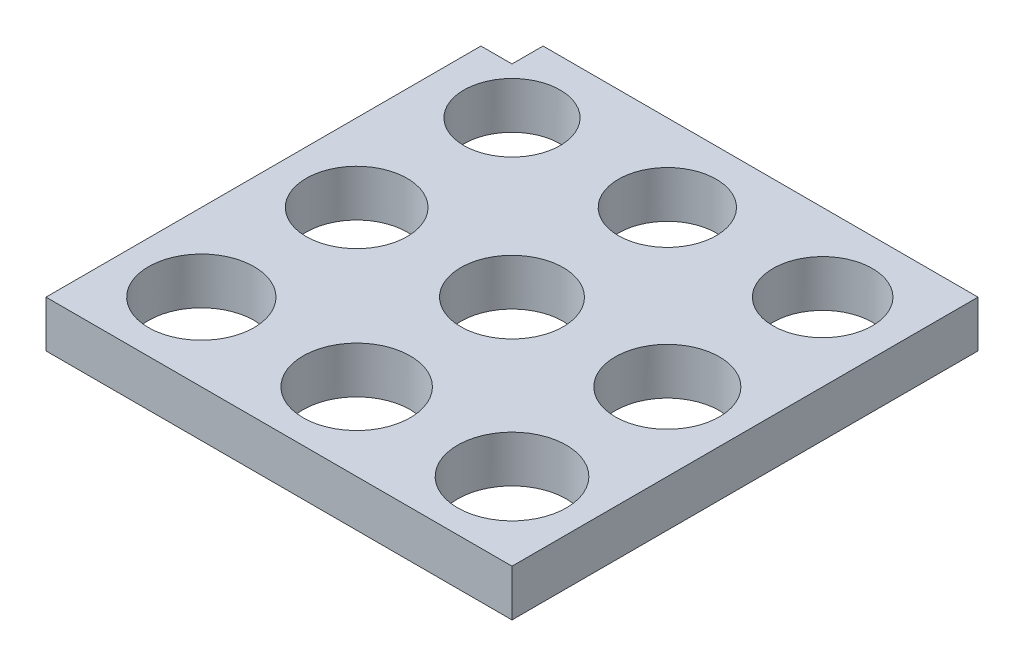
SolidWorks part; units mm, degrees
ref_plane "Front Plane" through (0, 0, 0) normal (0, 0, 1) x (1, 0, 0)
ref_plane "Top Plane" through (0, 0, 0) normal (0, 1, 0) x (1, 0, 0)
ref_plane "Right Plane" through (0, 0, 0) normal (1, 0, 0) x (0, 0, -1)
sketch "Sketch1" plane through (0, 0, 0) normal (0, 1, 0) x (1, 0, 0)
  line L1 (-7.5, -7.5) -> (7.5, -7.5)
  line L2 (-7.5, -7.5) -> (-7.5, 7.5)
  line L3 (-7.5, 7.5) -> (7.5, 7.5)
  line L4 (7.5, -7.5) -> (7.5, 7.5)
  line L5 (-7.5, -7.5) -> (7.5, 7.5) construction
  line L6 (-7.5, 7.5) -> (7.5, -7.5) construction
  point P0 (0, 0)
  dimension "D1" = 15
  dimension "D2" = 15
extrude "Boss-Extrude1" add sketch "Sketch1" along normal blind 1.5
sketch "Sketch2" plane through (0, 1.5, 0) normal (0, 1, 0) x (1, 0, 0)
  circle A5 centre (-5, 5) radius 1.55
  circle A22 centre (0, 5) radius 1.575
  circle A23 centre (5, 5) radius 1.6
  circle A24 centre (-5, 0) radius 1.625
  circle A25 centre (0, 0) radius 1.65
  circle A26 centre (5, 0) radius 1.675
  circle A27 centre (-5, -5) radius 1.7
  circle A28 centre (0, -5) radius 1.725
  circle A29 centre (5, -5) radius 1.75
  dimension "D1" = 3.15
  dimension "D9" = 3.1
  dimension "D2" = 3.2
  dimension "D3" = 3.25
  dimension "D4" = 3.3
  dimension "D5" = 3.35
  dimension "D6" = 3.4
  dimension "D7" = 3.45
  dimension "D8" = 3.5
extrude "Cut-Extrude1" cut sketch "Sketch2" against normal blind 10 contours A5 | A22 | A23 | A24 | A25 | A26 | A29 | A28 | A27 region at (-5, 1.5, -5)
sketch "Sketch4" plane through (0, 1.5, 0) normal (0, 1, 0) x (1, 0, 0)
  line L1 (-7.5, 7.5) -> (-6.5, 7.5)
  line L2 (-7.5, 7.5) -> (-7.5, 6.5)
  line L3 (-7.5, 6.5) -> (-6.5, 6.5)
  line L4 (-6.5, 7.5) -> (-6.5, 6.5)
  dimension "D1" = 1
  dimension "D2" = 1
extrude "Cut-Extrude2" cut sketch "Sketch4" against normal blind 10
